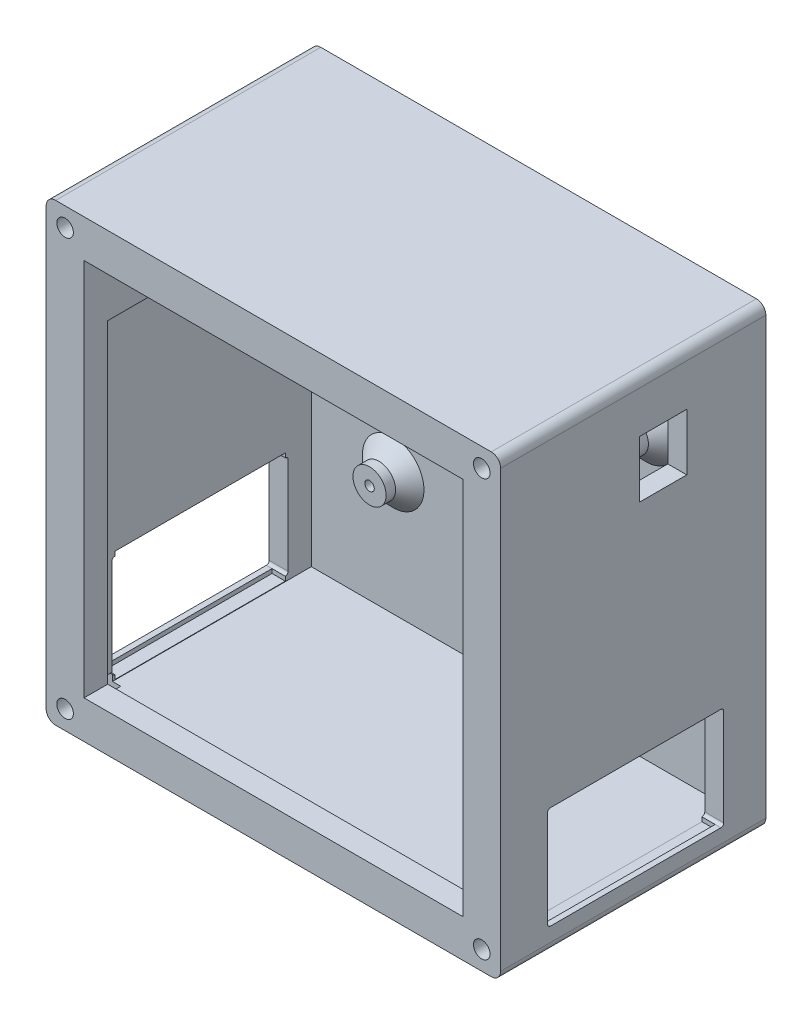
SolidWorks part; units mm, degrees
ref_plane "Front Plane" through (0, 0, 0) normal (0, 0, 1) x (1, 0, 0)
ref_plane "Top Plane" through (0, 0, 0) normal (0, 1, 0) x (1, 0, 0)
ref_plane "Right Plane" through (0, 0, 0) normal (1, 0, 0) x (0, 0, -1)
sketch "Sketch1" plane through (0, 0, 0) normal (0, 0, 1) x (1, 0, 0)
  line L0 (-36.576, -0.6604) -> (36.576, -0.6604) construction
  line L1 (-60.96, -60.96) -> (60.96, -60.96)
  line L2 (-60.96, -60.96) -> (-60.96, 60.96)
  line L3 (-60.96, 60.96) -> (60.96, 60.96)
  line L4 (60.96, -60.96) -> (60.96, 60.96)
  line L5 (-60.96, -60.96) -> (60.96, 60.96) construction
  line L6 (-60.96, 60.96) -> (60.96, -60.96) construction
  line L7 (-36.576, -25.8064) -> (36.576, -25.8064) construction
  line L8 (-36.576, -25.8064) -> (-36.576, 24.4856) construction
  line L9 (-36.576, 24.4856) -> (36.576, 24.4856) construction
  line L10 (36.576, -25.8064) -> (36.576, 24.4856) construction
  line L11 (-36.576, -25.8064) -> (36.576, 24.4856) construction
  line L12 (-36.576, 24.4856) -> (36.576, -25.8064) construction
  line L13 (0, 24.4856) -> (0, -25.8064) construction
  line L14 (-15.494, 39.5478) -> (54.61, 39.5478) construction
  line L15 (-15.494, 24.4856) -> (54.61, 24.4856) construction
  line L16 (-15.494, 24.4856) -> (-15.494, 54.61) construction
  line L17 (-15.494, 54.61) -> (54.61, 54.61) construction
  line L18 (54.61, 24.4856) -> (54.61, 54.61) construction
  line L19 (-15.494, 24.4856) -> (54.61, 54.61) construction
  line L20 (-15.494, 54.61) -> (54.61, 24.4856) construction
  line L21 (19.558, 54.61) -> (19.558, 24.4856) construction
  circle A0 centre (-33.909, -22.9489) radius 1.27
  circle A1 centre (33.909, -22.9489) radius 1.27
  circle A2 centre (33.909, 21.6281) radius 1.27
  circle A3 centre (-33.909, 21.6281) radius 1.27
  circle A4 centre (-13.208, 26.6573) radius 0.889
  circle A5 centre (52.324, 26.6573) radius 0.889
  circle A6 centre (52.324, 52.4383) radius 0.889
  circle A7 centre (-13.208, 52.4383) radius 0.889
  point P0 (0, 0)
  point P5 (0, -0.6604)
  point P24 (-0.2555, 0.0918)
  point P25 (19.558, 39.5478)
  dimension "D5" = 67.818
  dimension "D7" = 2.54
  dimension "D8" = 1.778
  dimension "D1" = 121.92
  dimension "D2" = 121.92
  dimension "D3" = 73.152
  dimension "D4" = 50.292
  dimension "D6" = 44.577
  dimension "D9" = 30.1244
  dimension "D10" = 70.104
  dimension "D11" = 25.781
  dimension "D12" = 65.532
  dimension "D13" = 6.35
  dimension "D14" = 6.35
extrude "Boss-Extrude1" add sketch "Sketch1" along normal blind 5.08
fillet "Fillet1" radius 2.54 4 edges at (-60.96, 60.96, 2.54) (60.96, 60.96, 2.54) (-60.96, -60.96, 2.54) (60.96, -60.96, 2.54)
sketch "Sketch3" plane through (0, 0, 5.08) normal (0, 0, 1) x (1, 0, 0)
  line L0 (55.88, 55.88) -> (-55.88, 55.88)
  line L1 (-55.88, 55.88) -> (-55.88, -55.88)
  line L2 (-55.88, -55.88) -> (55.88, -55.88)
  line L3 (55.88, -55.88) -> (55.88, 55.88)
  line L4 (58.42, 60.96) -> (-58.42, 60.96)
  line L5 (-60.96, 58.42) -> (-60.96, -58.42)
  line L6 (-58.42, -60.96) -> (58.42, -60.96)
  line L7 (60.96, -58.42) -> (60.96, 58.42)
  line L8 (58.42, 60.96) -> (-58.42, 60.96)
  line L9 (-60.96, 58.42) -> (-60.96, -58.42)
  line L10 (-58.42, -60.96) -> (58.42, -60.96)
  line L11 (60.96, -58.42) -> (60.96, 58.42)
  arc A0 (-55.88, 55.88) -> (-55.88, 55.88) centre (-55.88, 55.88) ccw
  arc A1 (-55.88, -55.88) -> (-55.88, -55.88) centre (-55.88, -55.88) ccw
  arc A2 (55.88, -55.88) -> (55.88, -55.88) centre (55.88, -55.88) ccw
  arc A3 (55.88, 55.88) -> (55.88, 55.88) centre (55.88, 55.88) ccw
  arc A4 (-58.42, 60.96) -> (-60.96, 58.42) centre (-58.42, 58.42) ccw
  arc A5 (-60.96, -58.42) -> (-58.42, -60.96) centre (-58.42, -58.42) ccw
  arc A6 (58.42, -60.96) -> (60.96, -58.42) centre (58.42, -58.42) ccw
  arc A7 (60.96, 58.42) -> (58.42, 60.96) centre (58.42, 58.42) ccw
  arc A8 (-58.42, 60.96) -> (-60.96, 58.42) centre (-58.42, 58.42) ccw
  arc A9 (-60.96, -58.42) -> (-58.42, -60.96) centre (-58.42, -58.42) ccw
  arc A10 (58.42, -60.96) -> (60.96, -58.42) centre (58.42, -58.42) ccw
  arc A11 (60.96, 58.42) -> (58.42, 60.96) centre (58.42, 58.42) ccw
  dimension "D1" = 0
  dimension "D2" = 5.08
extrude "Boss-Extrude2" add sketch "Sketch3" along normal blind 59.69
sketch "Sketch11" plane through (0, 0, 5.08) normal (0, 0, 1) x (1, 0, 0)
  circle A0 centre (52.324, 52.4383) radius 0.889 construction
  circle A1 centre (52.324, 26.6573) radius 0.889 construction
  circle A2 centre (33.909, 21.6281) radius 1.27 construction
  circle A3 centre (-13.208, 52.4383) radius 0.889 construction
  circle A4 centre (-13.208, 26.6573) radius 0.889 construction
  circle A5 centre (-33.909, -22.9489) radius 1.27 construction
  circle A6 centre (-33.909, 21.6281) radius 1.27 construction
  circle A7 centre (52.324, 52.4383) radius 0.889
  circle A8 centre (52.324, 26.6573) radius 0.889
  circle A9 centre (33.909, 21.6281) radius 1.27
  circle A10 centre (-13.208, 52.4383) radius 0.889
  circle A11 centre (-13.208, 26.6573) radius 0.889
  circle A12 centre (-33.909, -22.9489) radius 1.27
  circle A13 centre (-33.909, 21.6281) radius 1.27
  circle A14 centre (33.909, -22.9489) radius 1.27 construction
  circle A15 centre (33.909, -22.9489) radius 1.27
  circle A16 centre (52.324, 52.4383) radius 4.064
  circle A17 centre (52.324, 26.6573) radius 4.064
  circle A18 centre (33.909, 21.6281) radius 4.445
  circle A19 centre (-13.208, 52.4383) radius 4.064
  circle A20 centre (-13.208, 26.6573) radius 4.064
  circle A21 centre (-33.909, -22.9489) radius 4.445
  circle A22 centre (-33.909, 21.6281) radius 4.445
  circle A23 centre (33.909, -22.9489) radius 4.445
  dimension "D1" = 3.175
extrude "Boss-Extrude5" add sketch "Sketch11" along normal blind 6.35
sketch "Sketch5" plane through (60.96, 0, 0) normal (1, 0, 0) x (0, 0, -1)
  line L0 (-64.77, -55.88) -> (-5.08, -55.88) construction
  line L1 (-64.77, -55.88) -> (-5.08, -55.88) construction
  line L2 (-34.925, -58.42) -> (-34.925, 58.42) construction
  line L3 (-12.065, -54.61) -> (-57.785, -54.61)
  line L4 (-11.303, -53.848) -> (-11.303, -27.8638)
  line L5 (-12.065, -27.1018) -> (-57.785, -27.1018)
  line L6 (-58.547, -53.848) -> (-58.547, -27.8638)
  line L7 (-11.303, -54.61) -> (-58.547, -27.1018) construction
  line L8 (-11.303, -27.1018) -> (-58.547, -54.61) construction
  line L9 (-64.77, -58.42) -> (0, -58.42) construction
  line L10 (0, 58.42) -> (-64.77, 58.42) construction
  line L11 (-5.08, 55.88) -> (-5.08, -55.88) construction
  line L12 (-64.77, 55.88) -> (-64.77, -55.88) construction
  arc A0 (-11.303, -27.8638) -> (-12.065, -27.1018) centre (-12.065, -27.8638) ccw
  arc A1 (-12.065, -54.61) -> (-11.303, -53.848) centre (-12.065, -53.848) ccw
  arc A2 (-57.785, -54.61) -> (-58.547, -53.848) centre (-57.785, -53.848) cw
  arc A3 (-57.785, -27.1018) -> (-58.547, -27.8638) centre (-57.785, -27.8638) ccw
  point P2 (-34.925, -40.8559)
  dimension "D4" = 0.762
  dimension "D1" = 47.244
  dimension "D2" = 27.5082
  dimension "D3" = 2.54
extrude "Cut-Extrude1" cut sketch "Sketch5" against normal up to next
sketch "Sketch6" plane through (55.88, 0, 0) normal (-1, 0, 0) x (0, 0, 1)
  line L1 (57.785, -54.61) -> (12.065, -54.61) construction
  line L3 (12.065, -27.1018) -> (57.785, -27.1018) construction
  line L5 (57.785, -54.61) -> (12.065, -54.61)
  line L7 (12.065, -27.1018) -> (57.785, -27.1018)
  line L9 (12.065, -25.9588) -> (57.785, -25.9588)
  line L10 (57.785, -55.753) -> (12.065, -55.753)
  line L11 (57.785, -25.9588) -> (57.785, -27.1018)
  line L12 (12.065, -25.9588) -> (12.065, -27.1018)
  line L13 (12.065, -54.61) -> (12.065, -55.753)
  line L14 (57.785, -54.61) -> (57.785, -55.753)
  dimension "D1" = 1.143
extrude "Cut-Extrude2" cut sketch "Sketch6" against normal offset from surface (3.556 mm away) 1.524 up to face at (60.96, -40.8559, 34.925)
mirror "Mirror2" about plane through (0, 0, 0) normal (1, 0, 0) of "Cut-Extrude2", "Cut-Extrude1"
sketch "Sketch10" plane through (0, 0, 64.77) normal (0, 0, 1) x (1, 0, 0)
  line L0 (50.8, 50.8) -> (-50.8, 50.8)
  line L1 (-50.8, 50.8) -> (-50.8, -50.8)
  line L2 (-50.8, -50.8) -> (50.8, -50.8)
  line L3 (50.8, -50.8) -> (50.8, 50.8)
  line L4 (58.42, 60.96) -> (-58.42, 60.96)
  line L5 (-60.96, 58.42) -> (-60.96, -58.42)
  line L6 (-58.42, -60.96) -> (58.42, -60.96)
  line L7 (60.96, -58.42) -> (60.96, 58.42)
  line L8 (58.42, 60.96) -> (-58.42, 60.96)
  line L9 (-60.96, 58.42) -> (-60.96, -58.42)
  line L10 (-58.42, -60.96) -> (58.42, -60.96)
  line L11 (60.96, -58.42) -> (60.96, 58.42)
  arc A0 (50.8, 50.8) -> (50.8, 50.8) centre (50.8, 50.8) ccw
  arc A1 (-50.8, 50.8) -> (-50.8, 50.8) centre (-50.8, 50.8) ccw
  arc A2 (-50.8, -50.8) -> (-50.8, -50.8) centre (-50.8, -50.8) ccw
  arc A3 (50.8, -50.8) -> (50.8, -50.8) centre (50.8, -50.8) ccw
  arc A4 (60.96, 58.42) -> (58.42, 60.96) centre (58.42, 58.42) ccw
  arc A5 (-58.42, 60.96) -> (-60.96, 58.42) centre (-58.42, 58.42) ccw
  arc A6 (-60.96, -58.42) -> (-58.42, -60.96) centre (-58.42, -58.42) ccw
  arc A7 (58.42, -60.96) -> (60.96, -58.42) centre (58.42, -58.42) ccw
  arc A8 (60.96, 58.42) -> (58.42, 60.96) centre (58.42, 58.42) ccw
  arc A9 (-58.42, 60.96) -> (-60.96, 58.42) centre (-58.42, 58.42) ccw
  arc A10 (-60.96, -58.42) -> (-58.42, -60.96) centre (-58.42, -58.42) ccw
  arc A11 (58.42, -60.96) -> (60.96, -58.42) centre (58.42, -58.42) ccw
  point P24 (0, 0)
  point P25 (0, 0)
  dimension "D1" = 0
  dimension "D2" = 10.16
extrude "Boss-Extrude4" add sketch "Sketch10" along normal blind 6.35
chamfer "Chamfer1" distance 5.08 angle 45 4 edges at (0, -55.88, 64.77) (55.88, 0, 64.77) (0, 55.88, 64.77) (-55.88, 0, 64.77)
chamfer "Chamfer2" distance 3.81 angle 45 8 edges at (49.5309, 49.4862, 5.08) (48.26, 26.6573, 5.08) (29.464, -22.9489, 5.08) (29.464, 21.6281, 5.08) (-38.354, -22.9489, 5.08) (-38.354, 21.6281, 5.08) (-17.272, 26.6573, 5.08) (-13.208, 48.3743, 5.08)
sketch "Sketch13" plane through (55.88, 0, 0) normal (-1, 0, 0) x (0, 0, 1)
  line L0 (11.43, 25.7683) -> (11.43, 27.5463) construction
  line L1 (11.43, 51.5493) -> (11.43, 53.3273) construction
  line L2 (11.43, 25.7683) -> (11.43, 27.5463) construction
  line L3 (11.43, 51.5493) -> (11.43, 53.3273) construction
  line L4 (11.43, 51.5493) -> (11.43, 27.5463) construction
  line L5 (33.909, 31.9278) -> (21.209, 31.9278)
  line L6 (33.909, 31.9278) -> (33.909, 47.1678)
  line L7 (33.909, 47.1678) -> (21.209, 47.1678)
  line L8 (21.209, 31.9278) -> (21.209, 47.1678)
  line L9 (33.909, 31.9278) -> (21.209, 47.1678) construction
  line L10 (33.909, 47.1678) -> (21.209, 31.9278) construction
  point P4 (27.559, 39.5478)
  point P9 (11.43, 39.5478)
  dimension "D1" = 16.129
  dimension "D2" = 15.24
  dimension "D3" = 12.7
extrude "Cut-Extrude3" cut sketch "Sketch13" against normal up to next
sketch "Sketch16" plane through (-55.88, 0, 0) normal (1, 0, 0) x (0, 0, -1)
  line L0 (-59.69, 55.88) -> (-5.08, 55.88) construction
  line L1 (-24.13, 33.655) -> (-64.77, 33.655)
  line L2 (-24.13, 33.655) -> (-24.13, 55.88)
  line L3 (-24.13, 55.88) -> (-64.77, 55.88)
  line L4 (-59.69, 33.655) -> (-59.69, 55.88) construction
  line L5 (-24.13, 33.655) -> (-59.69, 55.88) construction
  line L6 (-24.13, 55.88) -> (-59.69, 33.655) construction
  line L8 (-59.69, 55.88) -> (-59.69, -55.88) construction
  line L9 (-64.77, 50.8) -> (-64.77, -50.8) construction
  line L10 (-64.77, 55.88) -> (-64.77, -50.8)
  point P0 (-41.91, 44.7675)
  point P7 (0, 0)
  point P13 (0, 0)
  line M17 (-5.08, 55.88) -> (-59.69, 55.88)
  line M18 (-59.69, 55.88) -> (-59.69, -55.88)
  dimension "D1" = 22.225
  dimension "D2" = 35.56
extrude "Boss-Extrude6" add sketch "Sketch16" along normal up to surface (5.08 mm away) contours L1 L2 M17 M18 | L3 L10 L1 M18 region at (-55.88, 44.7675, 41.91) region at (-55.88, 44.7675, 62.23) up to face at (-50.8, 0, 67.945)
sketch "Sketch17" plane through (0, 33.655, 0) normal (0, -1, 0) x (1, 0, 0)
  line L0 (-55.88, 24.13) -> (-55.88, 5.08) construction
  line L1 (-50.8, 24.13) -> (-55.88, 24.13) construction
  line L2 (-55.88, 24.13) -> (-55.88, 19.05)
  line L3 (-50.8, 24.13) -> (-55.88, 24.13)
  line L4 (-50.8, 24.13) -> (-55.88, 19.05)
  dimension "D1" = 45
extrude "Boss-Extrude7" add sketch "Sketch17" against normal up to next
sketch "Sketch18" plane through (-50.8, 0, 0) normal (1, 0, 0) x (0, 0, -1)
  line L2 (-24.13, 33.655) -> (-64.77, 33.655) construction
  line L3 (-24.13, 33.655) -> (-24.13, 55.88) construction
  line L4 (-24.13, 55.88) -> (-64.77, 55.88) construction
  line L6 (-24.13, 33.655) -> (-59.69, 33.655) construction
  line L7 (-24.13, 33.655) -> (-24.13, 55.88) construction
  line L8 (-24.13, 55.88) -> (-59.69, 55.88) construction
  line L10 (-59.69, 33.655) -> (-59.69, -55.88) construction
  line L11 (-59.69, 55.88) -> (-59.69, 33.655) construction
  line L12 (-59.69, 44.7675) -> (-24.13, 44.7675) construction
  line L13 (-41.91, 33.655) -> (-41.91, 55.88) construction
  circle A0 centre (-41.91, 44.7675) radius 6.35
  circle A1 centre (-54.61, 44.7675) radius 1.651
  circle A2 centre (-29.21, 44.7675) radius 1.651
  dimension "D1" = 12.7
  dimension "D2" = 3.302
  dimension "D3" = 25.4
extrude "Cut-Extrude4" cut sketch "Sketch18" against normal through all
sketch "Sketch19" plane through (0, 0, 71.12) normal (0, 0, 1) x (1, 0, 0)
  line L0 (0, 0) -> (-60.2161, -60.2161) construction
  line L2 (-58.42, -60.96) -> (58.42, -60.96) construction
  line L3 (-50.8, -50.8) -> (-50.8, -60.96) construction
  circle A0 centre (-55.88, -55.88) radius 2.2225
  arc A1 (-60.96, -58.42) -> (-58.42, -60.96) centre (-58.42, -58.42) ccw construction
  circle A2 centre (-55.88, 55.88) radius 2.2225
  circle A3 centre (55.88, 55.88) radius 2.2225
  circle A4 centre (55.88, -55.88) radius 2.2225
  point P8 (-50.8, -55.88)
  point P9 (0, 0)
  point P10 (55.88, 55.88)
  point P23 (0, 0)
  dimension "D1" = 4.445
  dimension "D2" = 4
extrude "Cut-Extrude5" cut sketch "Sketch19" against normal blind 12.7
